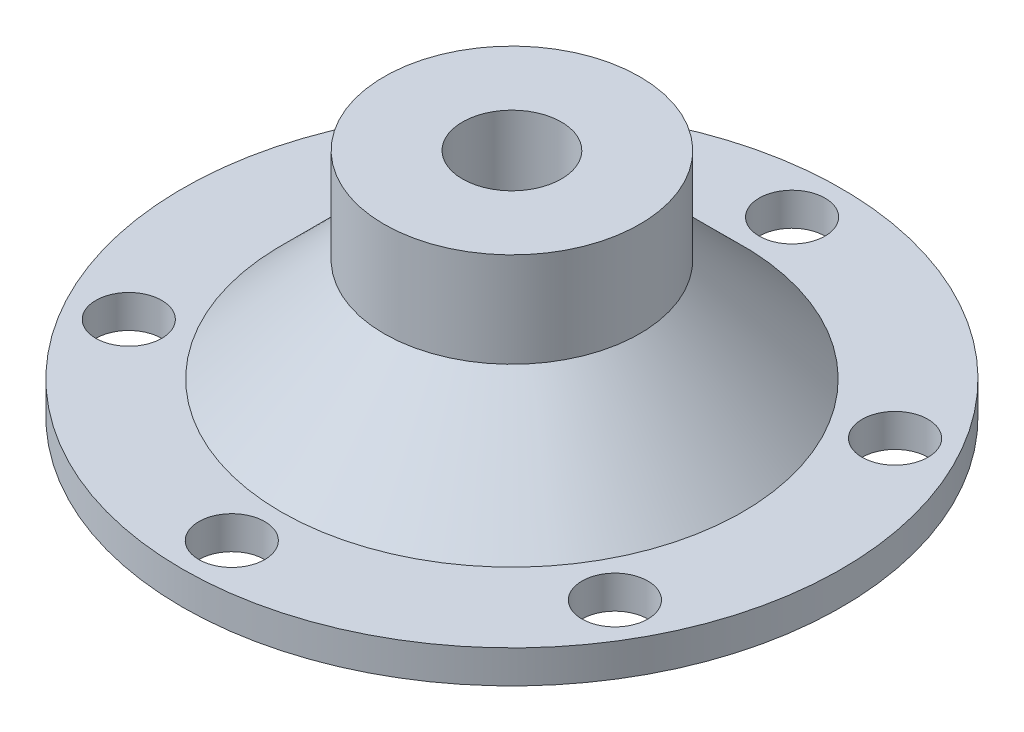
SolidWorks part; units mm, degrees
ref_plane "Front Plane" through (0, 0, 0) normal (0, 0, 1) x (1, 0, 0)
ref_plane "Top Plane" through (0, 0, 0) normal (0, 1, 0) x (1, 0, 0)
ref_plane "Right Plane" through (0, 0, 0) normal (1, 0, 0) x (0, 0, -1)
sketch "Sketch1" plane through (0, 0, 0) normal (0, 1, 0) x (1, 0, 0)
  circle A0 centre (0, 0) radius 127
extrude "Boss-Extrude1" add sketch "Sketch1" along normal blind 12.7
sketch "Sketch2" plane through (0, 12.7, 0) normal (0, 1, 0) x (1, 0, 0)
  circle A1 centre (0, 107.95) radius 12.7
  circle A2 centre (0, -107.95) radius 12.7
  circle A3 centre (-93.6625, -53.975) radius 12.7
  circle A4 centre (-93.6625, 53.975) radius 12.7
  circle A5 centre (93.6625, 53.975) radius 12.7
  circle A6 centre (93.6625, -53.975) radius 12.7
  dimension "D1" = 107.95
  dimension "D6" = 53.975
  dimension "D7" = 93.6625
  dimension "D2" = 107.95
  dimension "D3" = 53.975
  dimension "D4" = 53.975
  dimension "D5" = 53.975
  dimension "D8" = 93.6625
  dimension "D9" = 93.6625
  dimension "D10" = 93.6625
extrude "Cut-Extrude1" cut sketch "Sketch2" against normal blind 12.7
sketch "Sketch3" plane through (0, 12.7, 0) normal (0, 1, 0) x (1, 0, 0)
  circle A0 centre (0, 0) radius 88.9
extrude "Boss-Extrude2" add sketch "Sketch3" along normal blind 39.6875
chamfer "Chamfer1" distance 39.6875 1 edges at (0, 52.3875, 88.9)
sketch "Sketch4" plane through (0, 52.3875, 0) normal (0, 1, 0) x (1, 0, 0)
  circle A0 centre (0, 0) radius 49.2125
  circle A1 centre (0, 0) radius 19.05
extrude "Cut-Extrude5" cut sketch "Sketch4" against normal blind 88.4555 contours A1
sketch "Sketch5" plane through (0, 52.3875, 0) normal (0, 1, 0) x (1, 0, 0)
  circle A0 centre (0, 0) radius 19.05
  circle A1 centre (0, 0) radius 49.276
extrude "Boss-Extrude3" add sketch "Sketch5" along normal blind 36.5125
